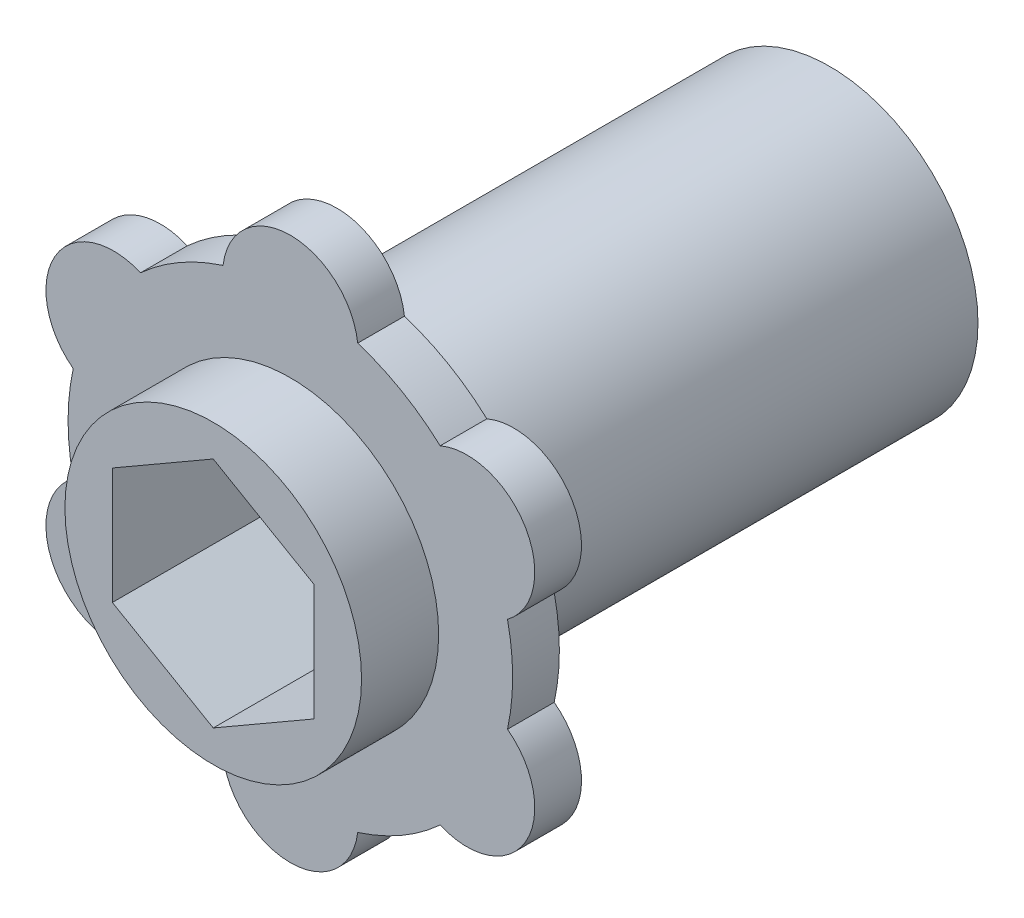
SolidWorks part; units mm, degrees
material "PET"
ref_plane "Front Plane" through (0, 0, 0) normal (0, 0, 1) x (1, 0, 0)
ref_plane "Top Plane" through (0, 0, 0) normal (0, 1, 0) x (1, 0, 0)
ref_plane "Right Plane" through (0, 0, 0) normal (1, 0, 0) x (0, 0, -1)
sketch "Sketch1" plane through (0, 0, 0) normal (0, 0, 1) x (1, 0, 0)
  line L0 (0, -13.0969) -> (0, 13.0969) construction
  line L1 (0, 7.479) -> (-6.477, 3.7395)
  line L2 (-6.477, 3.7395) -> (-6.477, -3.7395)
  line L3 (-6.477, -3.7395) -> (0, -7.479)
  line L4 (0, -7.479) -> (6.477, -3.7395)
  line L5 (6.477, -3.7395) -> (6.477, 3.7395)
  line L6 (6.477, 3.7395) -> (0, 7.479)
  arc A0 (-13.9434, 3.0582) -> (-13.9434, -3.0582) centre (0, 0) ccw
  circle A1 centre (0, 0) radius 6.477 construction
  arc A2 (4.3232, 13.6044) -> (-4.3232, 13.6044) centre (0, 13.0969) ccw
  arc A3 (13.9434, 3.0582) -> (9.6201, 10.5462) centre (11.3422, 6.5484) ccw
  arc A4 (9.6201, -10.5462) -> (13.9434, -3.0582) centre (11.3422, -6.5484) ccw
  arc A5 (-4.3232, -13.6044) -> (4.3232, -13.6044) centre (0, -13.0969) ccw
  arc A6 (-13.9434, -3.0582) -> (-9.6201, -10.5462) centre (-11.3422, -6.5484) ccw
  arc A7 (-9.6201, 10.5462) -> (-13.9434, 3.0582) centre (-11.3422, 6.5484) ccw
  arc A8 (-4.3232, 13.6044) -> (-9.6201, 10.5462) centre (0, 0) ccw
  arc A9 (9.6201, 10.5462) -> (4.3232, 13.6044) centre (0, 0) ccw
  arc A10 (13.9434, -3.0582) -> (13.9434, 3.0582) centre (0, 0) ccw
  arc A11 (4.3232, -13.6044) -> (9.6201, -10.5462) centre (0, 0) ccw
  arc A12 (-9.6201, -10.5462) -> (-4.3232, -13.6044) centre (0, 0) ccw
  point P13 (0, -10.0817)
  point P24 (0, 0)
  dimension "D1" = 28.5496
  dimension "D2" = 12.954
  dimension "D3" = 8.7058
  dimension "D4" = 13.0969
  dimension "D6" = 26.1937
  dimension "D5" = 6
extrude "Boss-Extrude1" add sketch "Sketch1" along normal mid plane 2.9997
sketch "Sketch2" plane through (0, 0, 1.4999) normal (0, 0, 1) x (1, 0, 0)
  line L1 (0, 7.479) -> (-6.477, 3.7395)
  line L2 (-6.477, 3.7395) -> (-6.477, -3.7395)
  line L3 (-6.477, -3.7395) -> (0, -7.479)
  line L4 (0, -7.479) -> (6.477, -3.7395)
  line L5 (6.477, -3.7395) -> (6.477, 3.7395)
  line L6 (6.477, 3.7395) -> (0, 7.479)
  circle A0 centre (0, 0) radius 6.477 construction
  circle A1 centre (0, 0) radius 9.525
  dimension "D1" = 19.05
extrude "Boss-Extrude2" add sketch "Sketch2" along normal blind 4.953
sketch "Sketch3" plane through (0, 0, -1.4999) normal (0, 0, -1) x (-1, 0, 0)
  line L1 (0, 7.479) -> (-6.477, 3.7395)
  line L2 (-6.477, 3.7395) -> (-6.477, -3.7395)
  line L3 (-6.477, -3.7395) -> (0, -7.479)
  line L4 (0, -7.479) -> (6.477, -3.7395)
  line L5 (6.477, -3.7395) -> (6.477, 3.7395)
  line L6 (6.477, 3.7395) -> (0, 7.479)
  circle A0 centre (0, 0) radius 6.477 construction
  circle A1 centre (0, 0) radius 9.525
  dimension "D1" = 19.05
extrude "Boss-Extrude3" add sketch "Sketch3" along normal blind 31.6332
